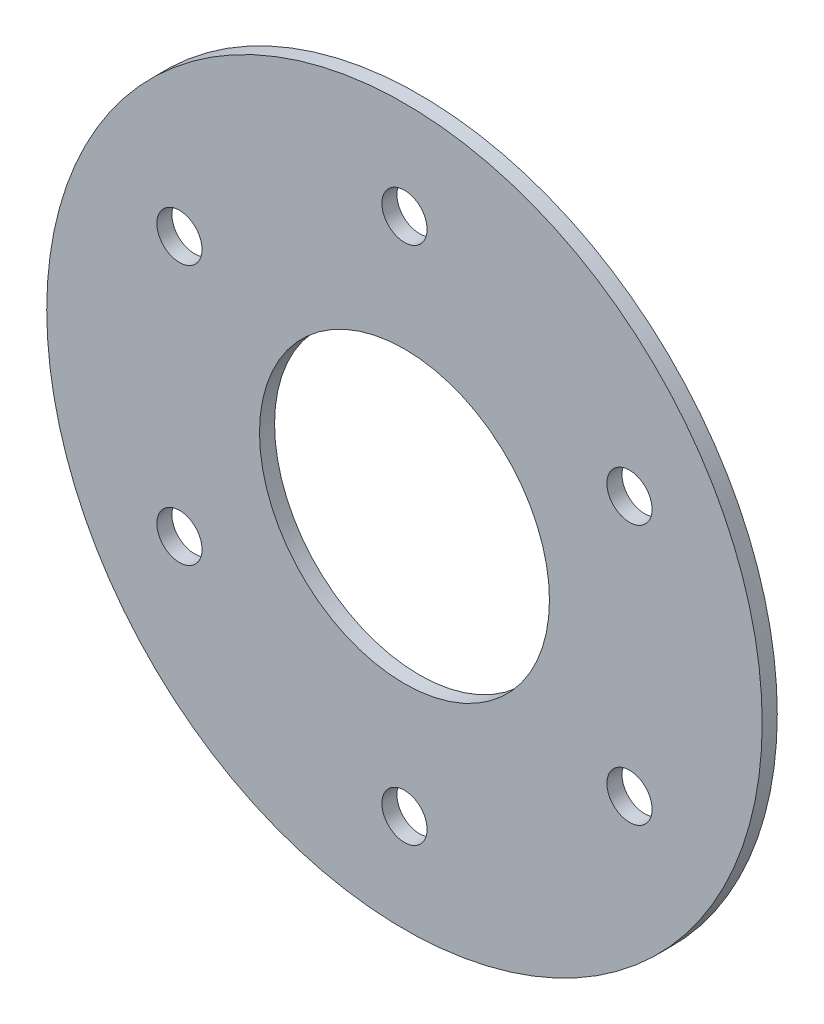
SolidWorks part; units mm, degrees
material "СТ3КП"
ref_plane "Спереди" through (0, 0, 0) normal (0, 0, 1) x (1, 0, 0)
ref_plane "Сверху" through (0, 0, 0) normal (0, 1, 0) x (1, 0, 0)
ref_plane "Справа" through (0, 0, 0) normal (1, 0, 0) x (0, 0, -1)
sketch "Эскиз1" plane through (0, 0, 0) normal (0, 0, 1) x (1, 0, 0)
  line L0 (0, 0) -> (0, 75) construction
  line L1 (0, 0) -> (0, 69) construction
  line L2 (0, 0) -> (59.7558, 34.5) construction
  line L3 (59.7558, 34.5) -> (0, 69) construction
  circle A0 centre (0, 0) radius 95
  circle A1 centre (0, 0) radius 38.5 construction
  circle A2 centre (0, 0) radius 38.5
  circle A3 centre (0, 69) radius 6
  circle A4 centre (59.7558, 34.5) radius 6
  circle A5 centre (59.7558, -34.5) radius 6
  circle A6 centre (0, -69) radius 6
  circle A7 centre (-59.7558, -34.5) radius 6
  circle A8 centre (-59.7558, 34.5) radius 6
  point P25 (0, 0)
  dimension "D1" = 6
base flange "Базовая кромка1" sketch "Эскиз1" thickness 4 reverse thickness direction yes parameters "D1"=1.5
sketch "Сгиб-Линии1" plane through (0, 0, 0) normal (0, 1, 0) x (1, 0, 0)
sketch "Граничная рамка1" plane through (0, 0, 0) normal (0, 1, 0) x (1, 0, 0)
sheet metal parameters "Листовой металл3" thickness 4 parameters "D1"=1.5
flat pattern "Развертка3" [suppressed]
sketch "Сгиб-Линии2" plane through (0, 0, 0) normal (0, 1, 0) x (1, 0, 0)
sketch "Граничная рамка2" [suppressed] plane through (0, 0, 0) normal (0, 1, 0) x (1, 0, 0)
